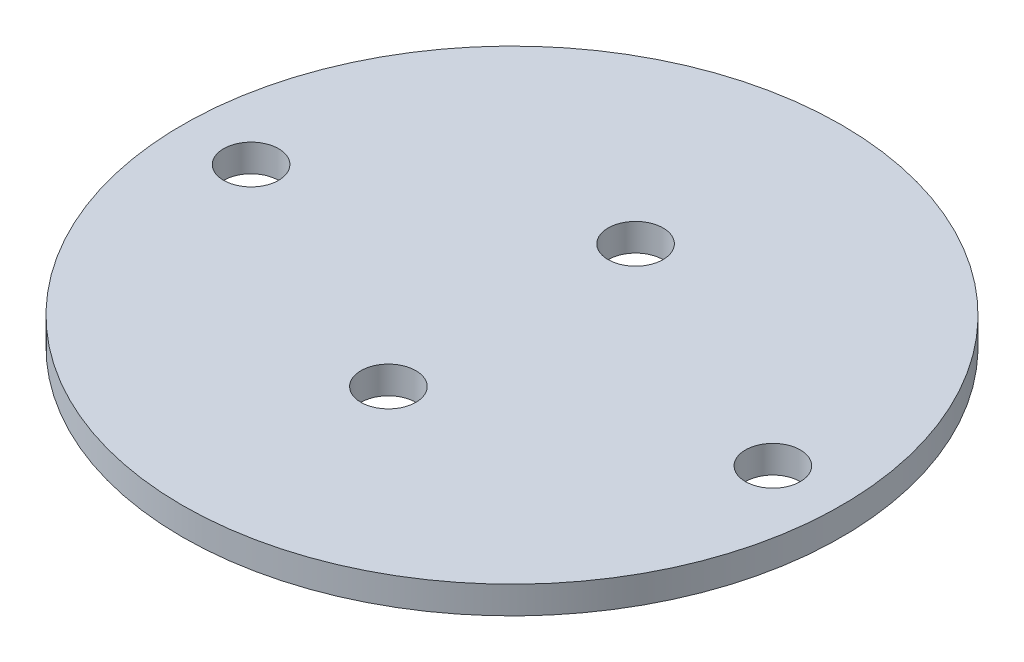
SolidWorks part; units mm, degrees
ref_plane "Front Plane" through (0, 0, 0) normal (0, 0, 1) x (1, 0, 0)
ref_plane "Top Plane" through (0, 0, 0) normal (0, 1, 0) x (1, 0, 0)
ref_plane "Right Plane" through (0, 0, 0) normal (1, 0, 0) x (0, 0, -1)
sketch "Sketch1" plane through (0, 0, 0) normal (0, 1, 0) x (1, 0, 0)
  line L0 (-24.5585, 0) -> (32.4415, 0) construction
  line L1 (3.9415, 0) -> (3.9415, 13.5)
  line L2 (3.9415, 0) -> (3.9415, -13.5)
  circle A0 centre (3.9415, 0) radius 36
  circle A1 centre (32.4415, 0) radius 3
  circle A2 centre (-24.5585, 0) radius 3
  circle A3 centre (3.9415, 13.5) radius 3
  circle A4 centre (3.9415, -13.5) radius 3
  circle A5 centre (-24.5585, 0) radius 6.25 construction
  circle A6 centre (3.9415, 13.5) radius 12.5 construction
  circle A7 centre (3.9415, -13.5) radius 12.5 construction
  circle A8 centre (32.4415, 0) radius 6.25 construction
  point P11 (3.9415, 0)
  dimension "D1" = 72
  dimension "D3" = 6
  dimension "D4" = 13.5
  dimension "D5" = 6
  dimension "D6" = 12.5
  dimension "D7" = 25
  dimension "D2" = 57
extrude "Boss-Extrude1" add sketch "Sketch1" against normal blind 3 contours A0 A4 A3 A2 A1 region at (-31.0403, 0, 0)
